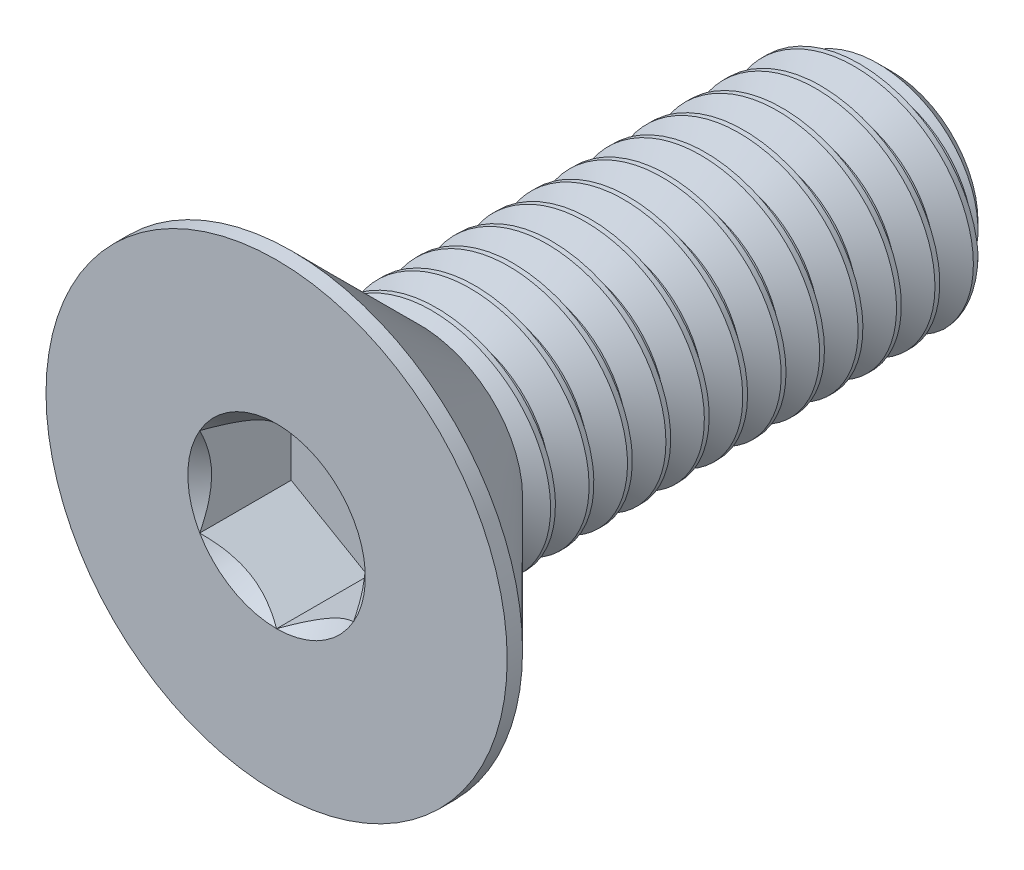
SolidWorks part; units mm, degrees
ref_plane "Front" through (0, 0, 0) normal (0, 0, 1) x (1, 0, 0)
ref_plane "Top" through (0, 0, 0) normal (0, 1, 0) x (1, 0, 0)
ref_plane "Right" through (0, 0, 0) normal (1, 0, 0) x (0, 0, -1)
sketch "Sketch1" plane through (0, 0, 0) normal (1, 0, 0) x (0, 0, -1)
  line L0 (0, 3) -> (0.2, 3) construction
  line L1 (0.2, 3) -> (1.7, 1.5) construction
  line L2 (0, 1.5) -> (8, 1.5)
  line L3 (8, 1.5) -> (8, 0)
  line L4 (8, 0) -> (0, 0)
  line L5 (0, 0) -> (0, 3) construction
  line L6 (0, 3) -> (0, -3) construction
  line L7 (8, 1.5) -> (8, -1.5) construction
  line L8 (0, -3) -> (0.2, -3) construction
  line L9 (0.2, -3) -> (1.7, -1.5) construction
  line L11 (0, 1.5) -> (0, 0)
  line L12 (1.7, 1.5) -> (1.7, 0) construction
revolve "Revolve1" add sketch "Sketch1" angle 360 mid plane about L4
sketch "Sketch3" plane through (0, 0, -8) normal (0, 0, -1) x (-1, 0, 0)
  circle A0 centre (0, 0) radius 1.5
curve "Helix/Spiral1" pitch 0.5 height 8 radius 1.5 centre (0, 0, -8) axis (0, 0, 1) start towards (0, 1, 0)
sketch "Sketch2" plane through (0, 0, 0) normal (1, 0, 0) x (0, 0, -1)
  line L0 (8, 1.5) -> (8.4375, 1.5)
  line L1 (8.4375, 1.5) -> (8.25, 1.1752)
  line L2 (8.25, 1.1752) -> (8.1875, 1.1752)
  line L3 (8.1875, 1.1752) -> (8, 1.5)
  line L4 (8.0938, 1.3376) -> (8.3437, 1.3376) construction
  dimension "D1" = 60
  dimension "D2" = 0.0625
  dimension "D3" = 0.25
chamfer "Chamfer1" distance 0.375 angle 45 1 edges at (0, 1.5, -8)
sweep "Cut-Sweep1" cut profiles "Sketch2" path "Helix/Spiral1" align with end faces yes
sketch "Sketch7" plane through (0, 0, 0) normal (1, 0, 0) x (0, 0, -1)
  line L0 (0, 3) -> (0.2, 3) construction
  line L1 (0.2, 3) -> (1.7, 1.5) construction
  line L2 (0, 3) -> (0.2, 3)
  line L3 (0.2, 3) -> (1.7, 1.5)
  line L4 (1.7, 1.5) -> (1.7, 0) construction
  line L5 (1.7, 1.5) -> (1.7, 0)
  line L7 (0, 0) -> (0, 3) construction
  line L8 (0, 0) -> (0, 3)
  line L9 (0, 0) -> (1.7, 0)
  line L10 (3.3, 0) -> (-3.3, 0) construction
revolve "Revolve2" add sketch "Sketch7" angle 360 mid plane about L9
ref_plane "Plane1" through (0, 0, -1.7) normal (0, 0, 1) x (1, 0, 0)
sketch "Sketch8" plane through (0, 0, -1.7) normal (0, 0, 1) x (1, 0, 0)
  circle A0 centre (0, 0) radius 1.5
extrude "Boss-Extrude1" add sketch "Sketch8" against normal through all draft 45
sketch "Sketch5" plane through (0, 0, 0) normal (0, 0, 1) x (1, 0, 0)
  line L1 (1, -0.5774) -> (1, 0.5774)
  line L2 (1, 0.5774) -> (0, 1.1547)
  line L3 (0, 1.1547) -> (-1, 0.5774)
  line L4 (-1, 0.5774) -> (-1, -0.5774)
  line L5 (-1, -0.5774) -> (0, -1.1547)
  line L6 (0, -1.1547) -> (1, -0.5774)
  circle A0 centre (0, 0) radius 1 construction
  dimension "Hex" = 2
extrude "Cut-Extrude2" cut sketch "Sketch5" against normal blind 1.19
sketch "Sketch6" plane through (0, 0, 0) normal (0, 0, 1) x (1, 0, 0)
  circle A0 centre (0, 0) radius 1.1547
extrude "Cut-Extrude3" cut sketch "Sketch6" against normal blind 1.19 draft 45
sketch "Sketch9" [suppressed] plane through (0, 0, -5.5) normal (0, 0, 1) x (1, 0, 0)
  circle A1 centre (0, 0) radius 5
  circle A2 centre (0, 0) radius 5
  point P0 (0, 5)
  dimension "D1" = 0
extrude "Boss-Extrude2" [suppressed] add sketch "Sketch9" against normal offset from surface (18.5 mm away) 26 up to face at (0, 1.125, -8)
fillet "Fillet1" [suppressed] radius 0.3
sketch "Sketch10" plane through (0, 0, 0) normal (1, 0, 0) x (0, 0, -1)
  line L0 (8, 1.5) -> (8, -1.5) construction
  point P0 (7.25, -1.5)
  dimension "D1" = 0.75
equation "\"D3@Helix/Spiral1\" = \"Lg@Sketch1\""
equation "\"D2@Sketch2\" = \"D4@Helix/Spiral1\" * .125"
equation "\"D3@Sketch2\" = \"D4@Helix/Spiral1\" * .5"
equation "\"D1@Chamfer1\" = \"D4@Helix/Spiral1\" * .75"
equation "\"D1@Cut-Extrude2\" = \"Head Ht@Sketch1\" * .7"
equation "\"D1@Sketch10\" = \"D4@Helix/Spiral1\" * 1.5"
equation "\"D1@Cut-Extrude3\" = \"D1@Cut-Extrude2\""
equation "\"D1@Fillet1\" = \"Dia@Sketch1\" * .1"
